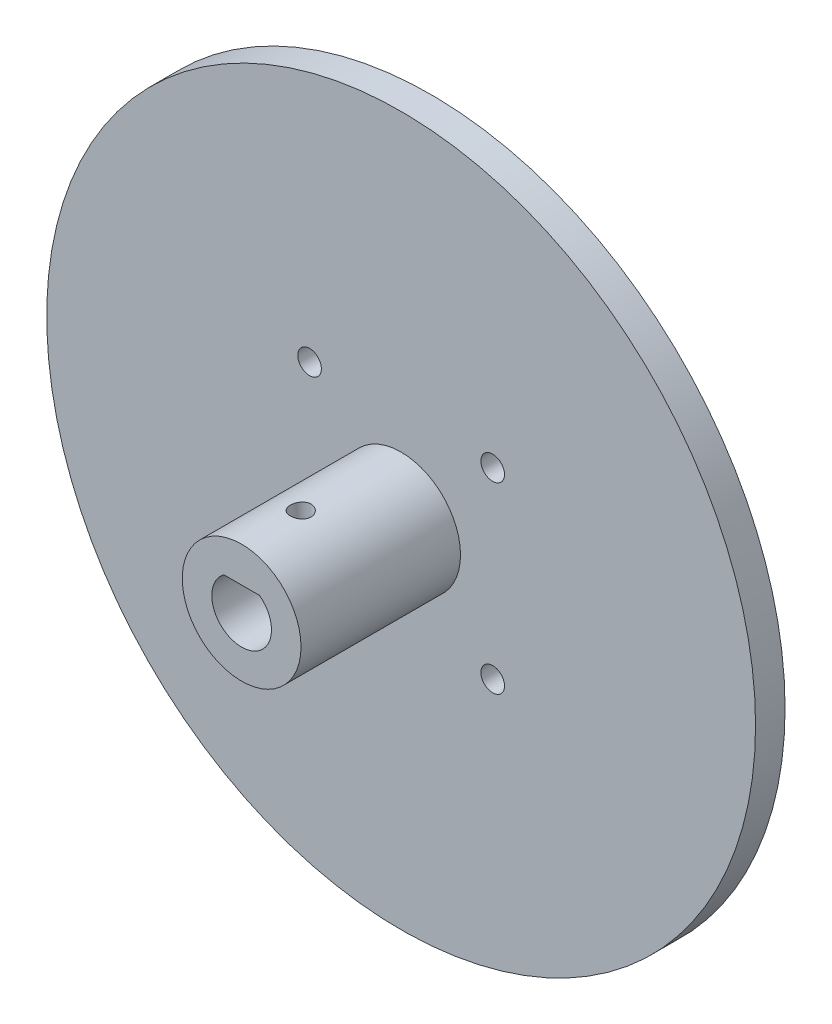
SolidWorks part; units mm, degrees
ref_plane "Front Plane" through (0, 0, 0) normal (0, 0, 1) x (1, 0, 0)
ref_plane "Top Plane" through (0, 0, 0) normal (0, 1, 0) x (1, 0, 0)
ref_plane "Right Plane" through (0, 0, 0) normal (1, 0, 0) x (0, 0, -1)
sketch "Sketch1" plane through (0, 0, 0) normal (0, 0, 1) x (1, 0, 0)
  line L1 (15.5, -15.5) -> (-15.5, -15.5) construction
  line L2 (15.5, -15.5) -> (15.5, 15.5) construction
  line L3 (15.5, 15.5) -> (-15.5, 15.5) construction
  line L4 (-15.5, -15.5) -> (-15.5, 15.5) construction
  line L5 (15.5, -15.5) -> (-15.5, 15.5) construction
  line L6 (15.5, 15.5) -> (-15.5, -15.5) construction
  circle A0 centre (0, 0) radius 60
  circle A1 centre (-15.5, 15.5) radius 2
  circle A2 centre (15.5, 15.5) radius 2
  circle A3 centre (15.5, -15.5) radius 2
  circle A4 centre (-15.5, -15.5) radius 2
  dimension "D1" = 120
  dimension "D3" = 4
  dimension "D4" = 2
  dimension "D2" = 31
  dimension "D5" = 2
extrude "Boss-Extrude1" add sketch "Sketch1" along normal blind 5
sketch "Sketch2" plane through (0, 0, 5) normal (0, 0, 1) x (1, 0, 0)
  line L0 (-3.0166, 4.05) -> (3.0166, 4.05)
  line L1 (0, 4.05) -> (0, -5.05)
  circle A0 centre (0, 0) radius 5.05
  circle A1 centre (0, 0) radius 10.05
  dimension "D1" = 10.1
  dimension "D2" = 9.1
  dimension "D3" = 5
extrude "Boss-Extrude2" add sketch "Sketch2" along normal blind 27 contours A1 A0 | L0 A0 region at (0, 4.4536, 5) region at (-9.7657, 0, 5)
sketch "Sketch3" plane through (0, 4.05, 0) normal (0, -1, 0) x (-1, 0, 0)
  line L0 (-10.05, -32) -> (10.05, -32) construction
  circle A0 centre (0, -22) radius 1.75
  dimension "D2" = 3.5
  dimension "D1" = 10
extrude "Cut-Extrude1" cut sketch "Sketch3" against normal blind 20 and the other way blind 20
